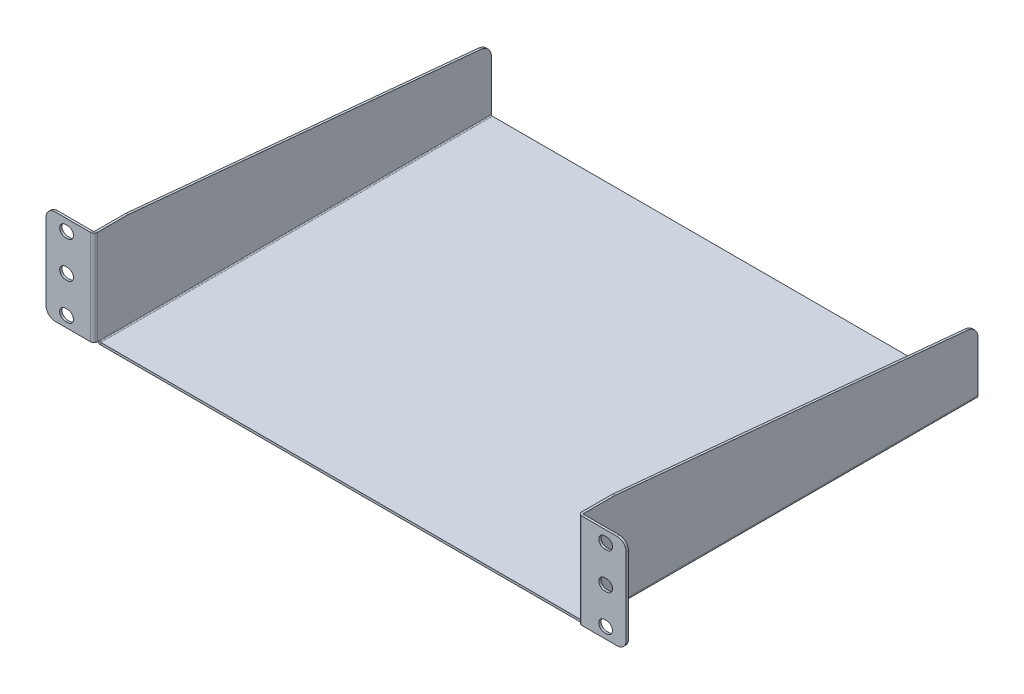
SolidWorks part; units mm, degrees
note: The reader was unsure of these and kept them because the rebuilt part matched: flange length of "Edge-Flange3", "Edge-Flange4", "Edge-Flange5", "Edge-Flange6".
ref_plane "Front Plane" through (0, 0, 0) normal (0, 0, 1) x (1, 0, 0)
ref_plane "Top Plane" through (0, 0, 0) normal (0, 1, 0) x (1, 0, 0)
ref_plane "Right Plane" through (0, 0, 0) normal (1, 0, 0) x (0, 0, -1)
sketch "Sketch1" plane through (0, 0, 0) normal (0, 1, 0) x (1, 0, 0)
  line L5 (-107, 87) -> (107, 87)
  line L6 (-107, 87) -> (-107, -87)
  line L7 (-107, -87) -> (107, -87)
  line L8 (107, 87) -> (107, -87)
  line L9 (-107, 87) -> (107, -87) construction
  line L10 (-107, -87) -> (107, 87) construction
  point P0 (0, 0)
  dimension "D1" = 214
  dimension "D2" = 174
base flange "Base-Flange1" sketch "Sketch1" thickness 1 reverse thickness direction no parameters "D1"=8
edge flange "Edge-Flange3" sketch "Sketch14" flange angle 90 flange length 43 flange position material inside bend radius 0.5 thickness 1 relief rectangular parameters "D6"=10
sketch "Sketch14" plane through (-107, 0, 0) normal (-1, 0, 0) x (0, 0, 1)
  line L0 (-87, 0) -> (87, 0) construction
  line L1 (-87, 0) -> (87, 0)
  line L2 (-87, 0) -> (-87, 42)
  line L3 (-87, 42) -> (87, 42)
  line L4 (87, 42) -> (87, 0)
bend "EdgeBend3" bend radius 0.5 bend angle 90 parameters "D5"=1
edge flange "Edge-Flange4" sketch "Sketch17" flange angle 90 flange length 43 flange position material inside bend radius 0.5 thickness 1 relief rectangular parameters "D6"=10
sketch "Sketch17" plane through (107, 0, 0) normal (1, 0, 0) x (0, 0, -1)
  line L0 (-87, 0) -> (87, 0) construction
  line L1 (-87, 0) -> (87, 0)
  line L2 (-87, 0) -> (-87, 42)
  line L3 (-87, 42) -> (87, 42)
  line L4 (87, 42) -> (87, 0)
bend "EdgeBend4" bend radius 0.5 bend angle 90 parameters "D5"=2
edge flange "Edge-Flange5" sketch "Sketch20" flange angle 90 flange length 21 flange position material inside bend radius 0.5 thickness 1 relief none parameters "D6"=10
sketch "Sketch20" plane through (107, 0, 87) normal (0, 0, 1) x (0, -1, 0)
  line L2 (-42, 0) -> (-42, 20)
  line L3 (-42, 20) -> (-0.5, 20)
  line L4 (-0.5, 20) -> (-0.5, 0)
  line L7 (-42, 0) -> (-0.5, 0) construction
  line L8 (-42, 0) -> (-0.5, 0)
bend "EdgeBend5" bend radius 0.5 bend angle 90 parameters "D5"=3
edge flange "Edge-Flange6" sketch "Sketch23" flange angle 90 flange length 21 flange position material inside bend radius 0.5 thickness 1 relief none parameters "D6"=10
sketch "Sketch23" plane through (-107, 0, 87) normal (0, 0, 1) x (0, 1, 0)
  line L0 (0.5, 0) -> (42, 0) construction
  line L1 (0.5, 0) -> (42, 0)
  line L2 (0.5, 0) -> (0.5, 20)
  line L3 (0.5, 20) -> (42, 20)
  line L4 (42, 20) -> (42, 0)
bend "EdgeBend6" bend radius 0.5 bend angle 90 parameters "D5"=4
fillet "Fillet1" radius 4 4 edges at (-127, 0.5, 86.5) (-127, 42, 86.5) (127, 0.5, 86.5) (127, 42, 86.5)
sketch "Sketch24" plane through (0, -1, 0) normal (0, -1, 0) x (1, 0, 0)
  line L0 (107, -87) -> (107, 85.5) construction
  line L1 (-107, 87) -> (107, 87)
  line L2 (-107, 87) -> (-107, 84.5)
  line L3 (-107, 84.5) -> (107, 84.5)
  line L4 (107, 87) -> (107, 84.5)
  dimension "D1" = 2.5
extrude "Cut-Extrude1" cut sketch "Sketch24" against normal up to surface (1.5 mm away) normal cut yes up to face at (115.25, 0.5, 86.5)
sketch "Sketch26" plane through (0, 0, 87) normal (0, 0, 1) x (1, 0, 0)
  line L0 (-118, 37) -> (-118, 5.24) construction
  line L1 (-118, 21.12) -> (-120.5, 21.12) construction
  line L3 (0, 0) -> (0, 21.12) construction
  line L4 (105.5, 0) -> (-105.5, 0) construction
  line L5 (0, 21.12) -> (-118, 21.12) construction
  line L6 (-118, 37) -> (-118, 42) construction
  line L7 (-107.5, 42) -> (-123, 42) construction
  circle A0 centre (-118, 37) radius 2.5
  circle A1 centre (-118, 5.24) radius 2.5
  circle A2 centre (-118, 21.12) radius 2.5
  circle A3 centre (118, 5.24) radius 2.5
  circle A4 centre (118, 21.12) radius 2.5
  circle A5 centre (118, 37) radius 2.5
  dimension "D1" = 31.76
  dimension "D2" = 5
  dimension "D3" = 118
  dimension "D4" = 5
extrude "Cut-Extrude2" cut sketch "Sketch26" against normal blind 10 normal cut yes
chamfer "Chamfer1" distance 1 angle 45 2 edges at (106.5, 42, -87) (-106.5, 42, -87)
sketch "Sketch32" plane through (0, 0, 86) normal (0, 0, -1) x (-1, 0, 0)
  line L0 (117.5, 37) -> (118.5, 37) construction
  line L1 (117.5, 39.5) -> (118.5, 39.5)
  line L2 (117.5, 34.5) -> (118.5, 34.5)
  line L3 (117.5, 21.12) -> (118.5, 21.12) construction
  line L4 (117.5, 23.62) -> (118.5, 23.62)
  line L5 (117.5, 18.62) -> (118.5, 18.62)
  line L6 (117.5, 5.24) -> (118.5, 5.24) construction
  line L7 (117.5, 7.74) -> (118.5, 7.74)
  line L8 (117.5, 2.74) -> (118.5, 2.74)
  line L9 (0, -1) -> (0, -11.9276) construction
  line L10 (-105.5, -1) -> (105.5, -1) construction
  arc A0 (117.5, 39.5) -> (117.5, 34.5) centre (117.5, 37) ccw
  arc A1 (118.5, 34.5) -> (118.5, 39.5) centre (118.5, 37) ccw
  arc A3 (117.5, 23.62) -> (117.5, 18.62) centre (117.5, 21.12) ccw
  arc A4 (118.5, 18.62) -> (118.5, 23.62) centre (118.5, 21.12) ccw
  arc A5 (117.5, 7.74) -> (117.5, 2.74) centre (117.5, 5.24) ccw
  arc A6 (118.5, 2.74) -> (118.5, 7.74) centre (118.5, 5.24) ccw
  point P2 (118, 37)
  point P15 (118, 21.12)
  point P22 (118, 5.24)
  dimension "D2" = 2.5
  dimension "D3" = 3
  dimension "D1" = 1
  dimension "D4" = 15.88
extrude "Cut-Extrude8" cut sketch "Sketch32" against normal through all normal cut yes
mirror "Mirror1" about plane through (0, 0, 0) normal (1, 0, 0) of "Cut-Extrude8"
sketch "Sketch39" plane through (0, 0, 86) normal (0, 0, -1) x (-1, 0, 0)
  line L0 (118, 39.5) -> (118, 34.5) construction
  line L1 (118.5, 39.5) -> (117.5, 39.5) construction
  line L2 (117.5, 34.5) -> (118.5, 34.5) construction
  line L3 (118, 23.62) -> (118, 18.62) construction
  line L4 (118.5, 23.62) -> (117.5, 23.62) construction
  line L5 (117.5, 18.62) -> (118.5, 18.62) construction
  line L6 (118, 7.74) -> (118, 2.74) construction
  line L7 (118.5, 7.74) -> (117.5, 7.74) construction
  line L8 (117.5, 2.74) -> (118.5, 2.74) construction
  circle A0 centre (118, 5.24) radius 2.5 construction
  circle A1 centre (118, 21.12) radius 2.5 construction
  circle A2 centre (118, 37) radius 2.5 construction
sketch "Sketch41" plane through (-107, 0, 0) normal (-1, 0, 0) x (0, 0, 1)
  line L0 (-87, 27) -> (72, 42)
  line L1 (-87, 41) -> (-87, 0.5) construction
  line L2 (85.5, 42) -> (-86, 42) construction
  line L3 (72, 42) -> (-87, 42)
  line L4 (-87, 42) -> (-87, 27)
  line L5 (87, 38) -> (87, 42) construction
  dimension "D1" = 15
  dimension "D2" = 15
extrude "Cut-Extrude9" cut sketch "Sketch41" against normal through all normal cut yes
fillet "Fillet2" radius 5 4 edges at (-106.5, 42, 72) (106.5, 42, 72) (106.5, 27, -87) (-106.5, 27, -87)
sketch "Bend-Lines1" [suppressed] plane through (0, 0, 0) normal (0, 1, 0) x (1, 0, 0)
sketch "Bounding-Box1" [suppressed] plane through (0, 0, 0) normal (0, 1, 0) x (1, 0, 0)
sheet metal parameters "Sheet-Metal1" thickness 1 parameters "D1"=8
flat pattern "Flat-Pattern1" [suppressed]
sketch "Bend-Lines2" plane through (0, 0, 0) normal (0, 1, 0) x (1, 0, 0)
sketch3d "Bounding-Box2" [suppressed]
  line L0 (-107, 115.25, 0) -> (-107, -115.25, 0) construction
  line L1 (107, 115.25, 0) -> (107, -115.25, 0) construction
  line L2 (-107, 115.25, 0) -> (107, 115.25, 0) construction
  line L3 (-107, -115.25, 0) -> (107, -115.25, 0) construction
sheet metal parameters "Sheet-Metal4" thickness 1 parameters "D1"=8
flat pattern "Flat-Pattern1"
sketch "Bend-Lines2" plane through (0, 0, 0) normal (0, 1, 0) x (1, 0, 0)
  line L0 (-107.2854, 115.25) -> (-107.2854, -115.25) construction
  line L1 (-107.2854, 115.25) -> (-107.2854, -115.25) construction
sketch3d "Bounding-Box2" [suppressed]
  line L0 (107, -115.25, 0) -> (-150.5708, -115.25, 0) construction
  line L1 (107, 115.25, 0) -> (-150.5708, 115.25, 0) construction
  line L2 (107, -115.25, 0) -> (107, 115.25, 0) construction
  line L3 (-150.5708, -115.25, 0) -> (-150.5708, 115.25, 0) construction
bend of the flat pattern "Flatten-<EdgeBend3>1"
sheet metal parameters "Sheet-Metal5" thickness 1 parameters "D1"=8
flat pattern "Flat-Pattern1"
sketch "Bend-Lines2" plane through (0, 0, 0) normal (0, 1, 0) x (1, 0, 0)
  line L0 (-107.2854, 115.25) -> (-107.2854, -115.25) construction
  line L1 (-107.2854, 115.25) -> (-107.2854, -115.25) construction
  line L2 (107.2854, -115.25) -> (107.2854, 115.25) construction
  line L3 (107.2854, -115.25) -> (107.2854, 115.25) construction
sketch3d "Bounding-Box2" [suppressed]
  line L0 (150.5708, -115.25, 0) -> (-150.5708, -115.25, 0) construction
  line L1 (150.5708, 115.25, 0) -> (-150.5708, 115.25, 0) construction
  line L2 (150.5708, -115.25, 0) -> (150.5708, 115.25, 0) construction
  line L3 (-150.5708, -115.25, 0) -> (-150.5708, 115.25, 0) construction
bend of the flat pattern "Flatten-<EdgeBend3>1"
bend of the flat pattern "Flatten-<EdgeBend4>1"
sheet metal parameters "Sheet-Metal6" thickness 1 parameters "D1"=8
flat pattern "Flat-Pattern1"
sketch "Bend-Lines2" plane through (0, 0, 0) normal (0, 1, 0) x (1, 0, 0)
  line L0 (-107.2854, 115.25) -> (-107.2854, -115.25) construction
  line L1 (-107.2854, 115.25) -> (-107.2854, -115.25) construction
  line L2 (107.2854, -115.25) -> (107.2854, 115.25) construction
  line L3 (107.2854, -115.25) -> (107.2854, 115.25) construction
  line L4 (108.0708, -114.5354) -> (150.5708, -114.5354) construction
  line L5 (108.0708, -114.5354) -> (150.5708, -114.5354) construction
sketch3d "Bounding-Box2" [suppressed]
  line L0 (150.5708, -133.8208, 0) -> (-150.5708, -133.8208, 0) construction
  line L1 (150.5708, 115.25, 0) -> (-150.5708, 115.25, 0) construction
  line L2 (150.5708, -133.8208, 0) -> (150.5708, 115.25, 0) construction
  line L3 (-150.5708, -133.8208, 0) -> (-150.5708, 115.25, 0) construction
bend of the flat pattern "Flatten-<EdgeBend3>1"
bend of the flat pattern "Flatten-<EdgeBend4>1"
bend of the flat pattern "Flatten-<EdgeBend5>1"
sheet metal parameters "Sheet-Metal7" thickness 1 parameters "D1"=8
flat pattern "Flat-Pattern1" [suppressed]
sketch "Bend-Lines2" plane through (0, 0, 0) normal (0, 1, 0) x (1, 0, 0)
  line L0 (-106.2854, -115.25) -> (-106.2854, 115.25) construction
  line L1 (-106.2854, -115.25) -> (-106.2854, 115.25) construction
  line L2 (106.2854, -115.25) -> (106.2854, 115.25) construction
  line L3 (106.2854, -115.25) -> (106.2854, 115.25) construction
  line L4 (107.0708, -114.5354) -> (148.5708, -114.5354) construction
  line L5 (107.0708, -114.5354) -> (148.5708, -114.5354) construction
  line L6 (-148.5708, -114.5354) -> (-107.0708, -114.5354) construction
  line L7 (-148.5708, -114.5354) -> (-107.0708, -114.5354) construction
sketch3d "Bounding-Box2" [suppressed]
  line L0 (-148.5708, -134.8206, 0) -> (148.5708, -134.8208, 0) construction
  line L1 (-148.5707, 115.25, 0) -> (148.5709, 115.2498, 0) construction
  line L2 (-148.5708, -134.8206, 0) -> (-148.5707, 115.25, 0) construction
  line L3 (148.5708, -134.8208, 0) -> (148.5709, 115.2498, 0) construction
bend of the flat pattern "Flatten-<EdgeBend3>1"
bend of the flat pattern "Flatten-<EdgeBend4>1"
bend of the flat pattern "Flatten-<EdgeBend5>1"
bend of the flat pattern "Flatten-<EdgeBend6>1"
sketch "Sketch27-1" [suppressed] plane through (106.5708, -1, 0) normal (0, -1, 0) x (0, 0, -1)
  circle A0 centre (-91.5, 36.25) radius 1.75
  circle A1 centre (-1.5, 36.25) radius 1.75
  circle A2 centre (88.5, 36.25) radius 1.75
  dimension "D1" = 3.5
sketch "Sketch30-1" [suppressed] plane through (-106.5708, -1, 0) normal (0, -1, 0) x (0, 0, 1)
  line L0 (-115.25, 42) -> (-115.25, -255.1416) construction
  line L1 (112.75, -1) -> (-115.25, -1) construction
  circle A0 centre (-51.1, 21) radius 1.75
  dimension "D1" = 64.15
  dimension "D3" = 3.5
  dimension "D2" = 22
sketch "Sketch31-1" [suppressed] plane through (-106.5708, -1, 0) normal (0, -1, 0) x (0, 0, 1)
  circle A0 centre (-108.45, 21) radius 1.75
  dimension "D1" = 3.5
sketch "Sketch34-1" [suppressed] plane through (-106.5708, -1, 0) normal (0, -1, 0) x (0, 0, 1)
  circle A0 centre (109.25, 21) radius 1.75
  dimension "D1" = 3.5
sheet metal parameters "Sheet-Metal8" thickness 1 parameters "D1"=8
flat pattern "Flat-Pattern1"
sketch "Bend-Lines2" plane through (0, 0, 0) normal (0, 1, 0) x (1, 0, 0)
  line L0 (-107.2854, 115.25) -> (-107.2854, -112.75) construction
  line L1 (-107.2854, 115.25) -> (-107.2854, -112.75) construction
  line L2 (107.2854, -112.75) -> (107.2854, 115.25) construction
  line L3 (107.2854, -112.75) -> (107.2854, 115.25) construction
  line L4 (108.0708, -114.5354) -> (150.5708, -114.5354) construction
  line L5 (108.0708, -114.5354) -> (150.5708, -114.5354) construction
  line L6 (-150.5708, -114.5354) -> (-108.0708, -114.5354) construction
  line L7 (-150.5708, -114.5354) -> (-108.0708, -114.5354) construction
sketch3d "Bounding-Box2" [suppressed]
  line L0 (-150.5708, -133.8208, 0) -> (150.5708, -133.8208, 0) construction
  line L1 (-150.5708, 115.25, 0) -> (150.5708, 115.25, 0) construction
  line L2 (-150.5708, -133.8208, 0) -> (-150.5708, 115.25, 0) construction
  line L3 (150.5708, -133.8208, 0) -> (150.5708, 115.25, 0) construction
bend of the flat pattern "Flatten-<EdgeBend3>1"
bend of the flat pattern "Flatten-<EdgeBend4>1"
bend of the flat pattern "Flatten-<EdgeBend5>1"
bend of the flat pattern "Flatten-<EdgeBend6>1"
sheet metal parameters "Sheet-Metal9" thickness 1 parameters "D1"=8
flat pattern "Flat-Pattern1"
sketch "Bend-Lines2" plane through (0, 0, 0) normal (0, 1, 0) x (1, 0, 0)
  line L0 (-106.2854, 115.25) -> (-106.2854, -112.75) construction
  line L1 (-106.2854, 115.25) -> (-106.2854, -112.75) construction
  line L2 (106.2854, -112.75) -> (106.2854, 115.25) construction
  line L3 (106.2854, -112.75) -> (106.2854, 115.25) construction
  line L4 (107.0708, -114.5354) -> (148.5708, -114.5354) construction
  line L5 (107.0708, -114.5354) -> (148.5708, -114.5354) construction
  line L6 (-148.5708, -114.5354) -> (-107.0708, -114.5354) construction
  line L7 (-148.5708, -114.5354) -> (-107.0708, -114.5354) construction
sketch3d "Bounding-Box2" [suppressed]
  line L0 (-148.5708, -134.8206, 0) -> (148.5708, -134.8208, 0) construction
  line L1 (-148.5707, 115.25, 0) -> (148.5709, 115.2498, 0) construction
  line L2 (-148.5708, -134.8206, 0) -> (-148.5707, 115.25, 0) construction
  line L3 (148.5708, -134.8208, 0) -> (148.5709, 115.2498, 0) construction
bend of the flat pattern "Flatten-<EdgeBend3>1"
bend of the flat pattern "Flatten-<EdgeBend4>1"
bend of the flat pattern "Flatten-<EdgeBend5>1"
bend of the flat pattern "Flatten-<EdgeBend6>1"
sheet metal parameters "Sheet-Metal15" thickness 1 parameters "D1"=8
flat pattern "Flat-Pattern1"
sketch "Bend-Lines2" plane through (0, 0, 0) normal (0, 1, 0) x (1, 0, 0)
  line L0 (-106.2854, 115.25) -> (-106.2854, -112.75) construction
  line L1 (-106.2854, 115.25) -> (-106.2854, -112.75) construction
  line L2 (106.2854, -112.75) -> (106.2854, 115.25) construction
  line L3 (106.2854, -112.75) -> (106.2854, 115.25) construction
  line L4 (107.0708, -114.5354) -> (148.5708, -114.5354) construction
  line L5 (107.0708, -114.5354) -> (148.5708, -114.5354) construction
  line L6 (-148.5708, -114.5354) -> (-107.0708, -114.5354) construction
  line L7 (-148.5708, -114.5354) -> (-107.0708, -114.5354) construction
sketch3d "Bounding-Box2" [suppressed]
  line L0 (-148.5708, -134.8206, 0) -> (148.5708, -134.8208, 0) construction
  line L1 (-148.5707, 115.25, 0) -> (148.5709, 115.2498, 0) construction
  line L2 (-148.5708, -134.8206, 0) -> (-148.5707, 115.25, 0) construction
  line L3 (148.5708, -134.8208, 0) -> (148.5709, 115.2498, 0) construction
bend of the flat pattern "Flatten-<EdgeBend3>1"
bend of the flat pattern "Flatten-<EdgeBend4>1"
bend of the flat pattern "Flatten-<EdgeBend5>1"
bend of the flat pattern "Flatten-<EdgeBend6>1"
sheet metal parameters "Sheet-Metal16" thickness 1 parameters "D1"=8
flat pattern "Flat-Pattern1" [suppressed]
sketch "Bend-Lines2" plane through (0, 0, 0) normal (0, 1, 0) x (1, 0, 0)
  line L0 (-106.2854, 87) -> (-106.2854, -84.5) construction
  line L1 (-106.2854, 87) -> (-106.2854, -84.5) construction
  line L2 (106.2854, -84.5) -> (106.2854, 87) construction
  line L3 (106.2854, -84.5) -> (106.2854, 87) construction
  line L4 (107.0708, -86.2854) -> (148.5708, -86.2854) construction
  line L5 (107.0708, -86.2854) -> (148.5708, -86.2854) construction
  line L6 (-148.5708, -86.2854) -> (-107.0708, -86.2854) construction
  line L7 (-148.5708, -86.2854) -> (-107.0708, -86.2854) construction
sketch3d "Bounding-Box2" [suppressed]
  line L0 (-148.5708, -106.5706, 0) -> (148.5708, -106.5708, 0) construction
  line L1 (-148.5707, 87, 0) -> (148.5709, 86.9998, 0) construction
  line L2 (-148.5708, -106.5706, 0) -> (-148.5707, 87, 0) construction
  line L3 (148.5708, -106.5708, 0) -> (148.5709, 86.9998, 0) construction
bend of the flat pattern "Flatten-<EdgeBend3>1"
bend of the flat pattern "Flatten-<EdgeBend4>1"
bend of the flat pattern "Flatten-<EdgeBend5>1"
bend of the flat pattern "Flatten-<EdgeBend6>1"
sketch "Sketch39-1" [suppressed] plane through (-106.5708, -1, -20.4292) normal (0, -1, 0) x (0, 0, 1)
  line L0 (118, 39.5) -> (118, 34.5) construction
  line L3 (118, 23.62) -> (118, 18.62) construction
  line L6 (118, 7.74) -> (118, 2.74) construction
  circle A0 centre (118, 5.24) radius 2.5 construction
  circle A1 centre (118, 21.12) radius 2.5 construction
  circle A2 centre (118, 37) radius 2.5 construction
sheet metal parameters "Sheet-Metal21" thickness 1 parameters "D1"=8
flat pattern "Flat-Pattern1" [suppressed]
sketch "Bend-Lines2" plane through (0, 0, 0) normal (0, 1, 0) x (1, 0, 0)
  line L0 (-106.2854, 87) -> (-106.2854, -84.5) construction
  line L1 (-106.2854, 87) -> (-106.2854, -84.5) construction
  line L2 (106.2854, -84.5) -> (106.2854, 87) construction
  line L3 (106.2854, -84.5) -> (106.2854, 87) construction
  line L4 (107.0708, -86.2854) -> (148.5708, -86.2854) construction
  line L5 (107.0708, -86.2854) -> (148.5708, -86.2854) construction
  line L6 (-148.5708, -86.2854) -> (-107.0708, -86.2854) construction
  line L7 (-148.5708, -86.2854) -> (-107.0708, -86.2854) construction
sketch3d "Bounding-Box2" [suppressed]
  line L0 (-148.5708, -106.5707, 0) -> (148.5708, -106.5708, 0) construction
  line L1 (-148.5708, 87, 0) -> (148.5708, 87, 0) construction
  line L2 (-148.5708, -106.5707, 0) -> (-148.5708, 87, 0) construction
  line L3 (148.5708, -106.5708, 0) -> (148.5708, 87, 0) construction
bend of the flat pattern "Flatten-<EdgeBend3>1"
bend of the flat pattern "Flatten-<EdgeBend4>1"
bend of the flat pattern "Flatten-<EdgeBend5>1"
bend of the flat pattern "Flatten-<EdgeBend6>1"
sketch "Sketch39-1" [suppressed] plane through (-106.5708, -1, -20.4292) normal (0, -1, 0) x (0, 0, 1)
  line L0 (118, 39.5) -> (118, 34.5) construction
  line L3 (118, 23.62) -> (118, 18.62) construction
  line L6 (118, 7.74) -> (118, 2.74) construction
  circle A0 centre (118, 5.24) radius 2.5 construction
  circle A1 centre (118, 21.12) radius 2.5 construction
  circle A2 centre (118, 37) radius 2.5 construction
